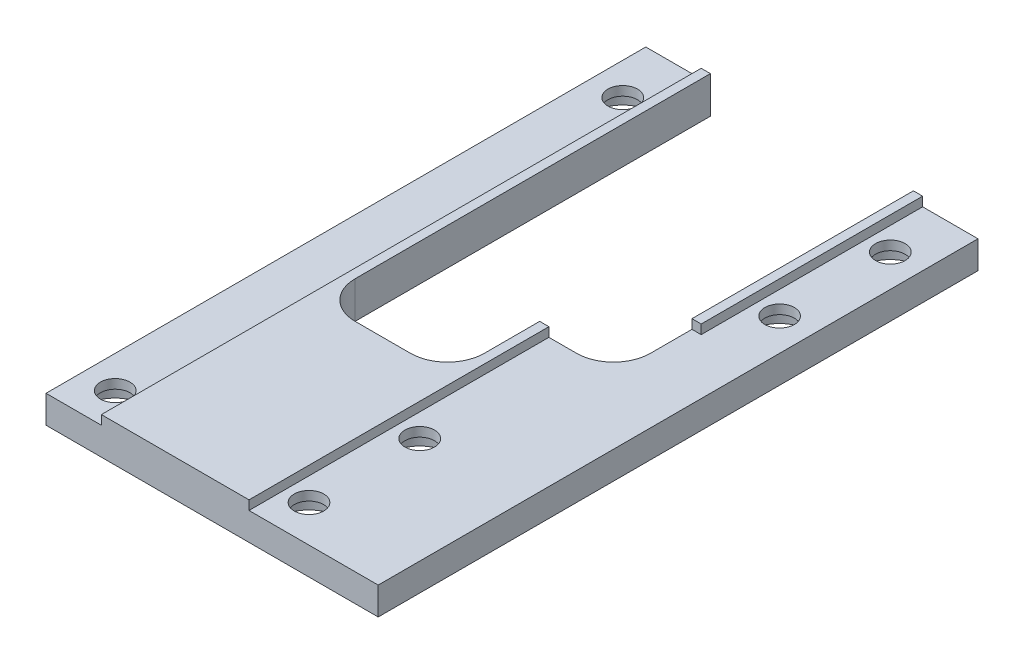
SolidWorks part; units mm, degrees
ref_plane "Ebene vorne" through (0, 0, 0) normal (0, 0, 1) x (1, 0, 0)
ref_plane "Ebene oben" through (0, 0, 0) normal (0, 1, 0) x (1, 0, 0)
ref_plane "Ebene rechts" through (0, 0, 0) normal (1, 0, 0) x (0, 0, -1)
sketch "Skizze1" plane through (0, 0, 0) normal (0, 1, 0) x (1, 0, 0)
  line L0 (0, 32.5) -> (0, -32.5) construction
  line L1 (-18, 32.5) -> (18, 32.5)
  line L2 (-18, 32.5) -> (-18, -32.5)
  line L3 (-18, -32.5) -> (18, -32.5)
  line L4 (18, 32.5) -> (18, -32.5)
  dimension "D1" = 36
  dimension "D4" = 65
extrude "Aufsatz-Linear austragen1" add sketch "Skizze1" along normal blind 4
sketch "Skizze2" plane through (0, 4, 0) normal (0, 1, 0) x (1, 0, 0)
  line L0 (-18, -32.5) -> (18, -32.5) construction
  line L1 (-18, 32.5) -> (-12, 32.5)
  line L2 (-18, 32.5) -> (-18, -32.5)
  line L3 (-18, -32.5) -> (-12, -32.5)
  line L4 (-12, 32.5) -> (-12, -32.5)
  line L5 (18, 32.5) -> (12, 32.5)
  line L6 (18, 32.5) -> (18, -32.5)
  line L7 (18, -32.5) -> (4, -32.5)
  line L8 (12, 32.5) -> (12, 8.5)
  line L9 (0, 32.5) -> (0, 0) construction
  line L10 (18, 32.5) -> (-18, 32.5) construction
  line L11 (-11, 32.5) -> (11, 32.5)
  line L12 (-11, 32.5) -> (-11, 0)
  line L14 (11, 32.5) -> (11, 0)
  line L15 (12, 8.5) -> (4, 8.5)
  line L16 (-11, 0) -> (11, 0)
  line L17 (4, 8.5) -> (4, -32.5)
  line L18 (-11, 0) -> (3, 0)
  line L19 (-11, 0) -> (-11, -10)
  line L20 (-11, -10) -> (3, -10)
  line L21 (3, 0) -> (3, -10)
  dimension "D3" = 1
  dimension "D1" = 16
  dimension "D2" = 6
  dimension "D4" = 24
  dimension "D5" = 0
  dimension "D6" = 10
  dimension "D7" = 1
extrude "Schnitt-Linear austragen1" cut sketch "Skizze2" against normal blind 1 contours L4 L3 L2 L1 | L8 L15 L17 L7 L6 L5
extrude "Schnitt-Linear austragen2" cut sketch "Skizze2<3>" against normal through all contours L16 L14 L11 L12 | L19 L20 L21 L18
sketch "Skizze2<3>" plane through (0, 4, 0) normal (0, 1, 0) x (1, 0, 0) same geometry as "Skizze2"
fillet "Verrundung1" radius 4 3 edges at (11, 1.5, 0) (3, 2, 10) (-11, 2, 10)
hole_wizard "Stirnsenkung für  M3 Zylinderschraube mit Schlitz/Kreuzschlitz1" positions "Skizze6" profile "Skizze5" counterbore size "M3" standard "DIN" end condition through all
sketch "Skizze6" plane through (0, 0, 0) normal (0, -1, 0) x (-1, 0, 0)
  line L2 (-14.5, 26.5) -> (14.5, 26.5) construction
  line L3 (14.5, 26.5) -> (14.5, -28.5) construction
  line L7 (14.5, -28.5) -> (14.5, -32.5) construction
  line L9 (14.5, 26.5) -> (14.5, 32.5) construction
  line L17 (11, 32.5) -> (18, 32.5) construction
  line L18 (18, -32.5) -> (-18, -32.5) construction
  line L19 (-6.5, -28.5) -> (-6.5, -16.5) construction
  line L21 (-14.5, 26.5) -> (-14.5, 14.5) construction
  line L24 (0, 0) -> (0, 26.5) construction
  line L26 (14.5, -28.5) -> (-6.5, -28.5) construction
  line L27 (-6.5, -16.5) -> (-4, -16.5) construction
  line L28 (-4, 0) -> (-4, -32.5) construction
  line L30 (12, 32.5) -> (12, -32.5) construction
  line L31 (12, -16.5) -> (14.5, -16.5) construction
  point P0 (14.5, -28.5)
  point P2 (14.5, 26.5)
  point P6 (-14.5, 26.5)
  point P56 (-6.5, -28.5)
  point P58 (-6.5, -16.5)
  point P60 (-14.5, 14.5)
  dimension "D1" = 4
  dimension "D2" = 6
  dimension "D3" = 12
sketch "Skizze5" plane through (-14.5, 0, 28.5) normal (1, 0, 0) x (0, 0, -1)
  line L0 (0, 0) -> (0, 4)
  line L1 (0, 4) -> (1.6, 4)
  line L3 (1.6, 4) -> (1.6, 2)
  line L4 (1.6, 2) -> (3.25, 2)
  line L5 (3.25, 2) -> (3.25, 0)
  line L7 (3.25, 0) -> (0, 0)
  line L11 (0, -6.35) -> (0, 107.95) construction
  dimension "Bohrerdurchmesser" = 3.2
  dimension "Bohrungstiefe" = 4
  dimension "Senkdurchmesser2" = 6.5
  dimension "Senktiefe2" = 2
